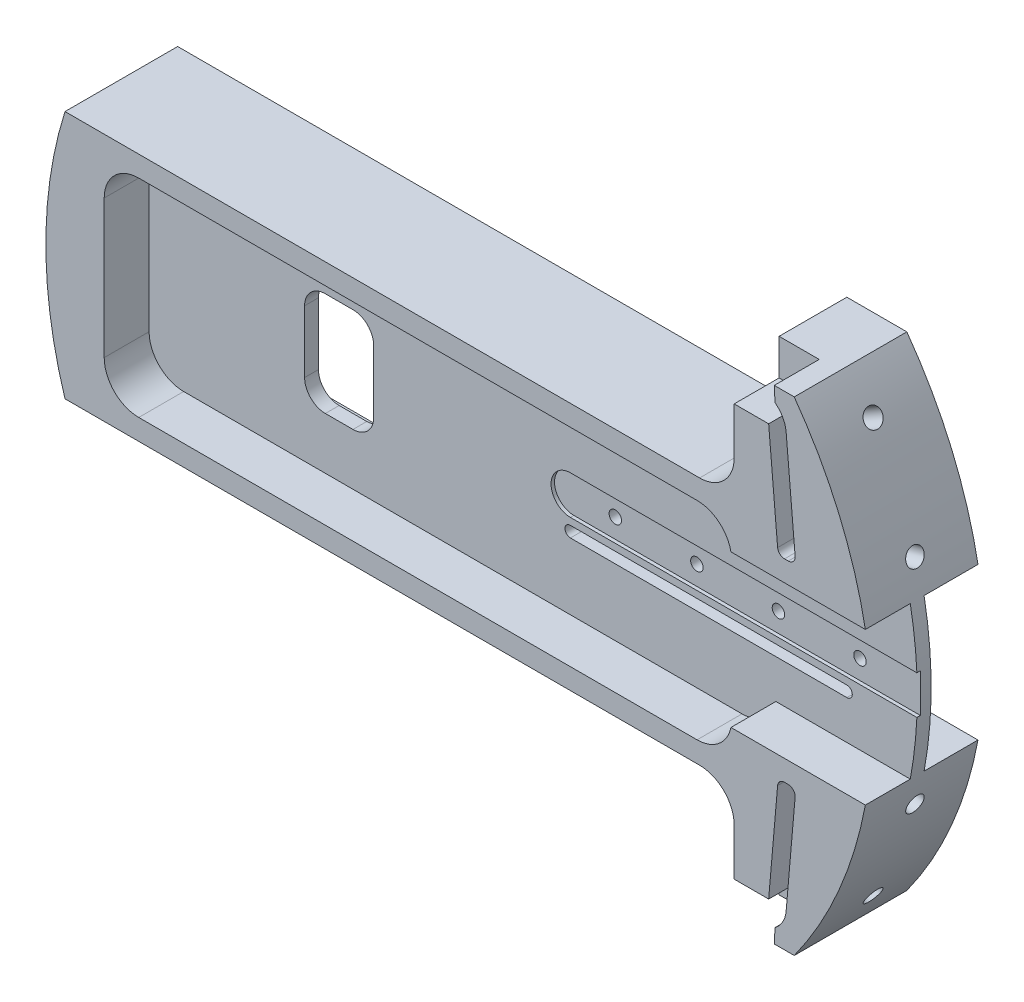
SolidWorks part; units mm, degrees
ref_plane "Front Plane" through (0, 0, 0) normal (0, 0, 1) x (1, 0, 0)
ref_plane "Top Plane" through (0, 0, 0) normal (0, 1, 0) x (1, 0, 0)
ref_plane "Right Plane" through (0, 0, 0) normal (1, 0, 0) x (0, 0, -1)
sketch "Sketch1" plane through (0, 0, 0) normal (0, 0, 1) x (1, 0, 0)
  line L0 (0, 0) -> (91.8237, 0) construction
  line L2 (-71.5726, 25.4) -> (-65.2226, 25.4)
  line L3 (50.546, 44.45) -> (50.546, 22.86)
  line L4 (50.546, -44.45) -> (50.546, -22.86)
  line L5 (44.196, -16.51) -> (-58.8726, -16.51)
  line L6 (50.546, 44.45) -> (61.5792, 44.45)
  line L7 (50.546, -44.45) -> (61.5792, -44.45)
  line L8 (-65.2226, -22.86) -> (-65.2226, -25.4)
  line L9 (44.196, 16.51) -> (-58.8726, 16.51)
  line L10 (-65.2226, 22.86) -> (-65.2226, 25.4)
  line L11 (-71.5726, -25.4) -> (-65.2226, -25.4)
  arc A0 (61.5792, -44.45) -> (61.5792, 44.45) centre (0, 0) ccw
  circle A1 centre (0, 0) radius 75.946 construction
  arc A2 (-71.5726, 25.4) -> (-71.5726, -25.4) centre (0, 0) ccw
  arc A5 (50.546, 22.86) -> (44.196, 16.51) centre (44.196, 22.86) cw
  arc A6 (-58.8726, 16.51) -> (-65.2226, 22.86) centre (-58.8726, 22.86) cw
  arc A7 (50.546, -22.86) -> (44.196, -16.51) centre (44.196, -22.86) ccw
  arc A8 (-58.8726, -16.51) -> (-65.2226, -22.86) centre (-58.8726, -22.86) ccw
  point P6 (75.946, 0)
  point P17 (0, 0)
  point P30 (50.546, -16.51)
  point P33 (-65.2226, -16.51)
  dimension "D1" = 75.946
  dimension "D8" = 151.892
  dimension "D11" = 75.946
  dimension "D13" = 6.35
  dimension "D2" = 27.94
  dimension "D3" = 6.35
  dimension "D4" = 11.0332
  dimension "D5" = 50.8
  dimension "D6" = 88.9
extrude "Boss-Extrude1" add sketch "Sketch1" along normal blind 2.54
sketch "Sketch2" plane through (0, 0, 2.54) normal (0, 0, 1) x (1, 0, 0)
  line L0 (60.2463, 17.78) -> (56.2059, 64.1603) construction
  line L1 (-13.9228, 0) -> (116.9939, 0) construction
  line L2 (35.7924, 17.78) -> (109.7023, 17.78) construction
  line L3 (61.8653, 17.78) -> (60.0951, 38.1)
  line L4 (58.6516, 17.5) -> (56.8815, 37.82)
  line L5 (56.8815, 37.82) -> (50.546, 37.82)
  line L6 (58.0471, 41.7789) -> (57.9008, 44.704)
  line L7 (57.9008, 44.704) -> (61.395, 44.704)
  line L8 (50.546, 37.82) -> (50.546, 16.5667)
  line L9 (50.546, 16.5667) -> (57.3661, 16.5667)
  line L10 (60.7595, 15.0941) -> (60.7595, 13.5449)
  line L11 (60.7595, 13.5449) -> (74.7284, 13.5449)
  line L12 (60.2463, -17.78) -> (56.2059, -64.1603) construction
  line L13 (60.7595, -13.5449) -> (74.7284, -13.5449)
  line L14 (60.7595, -15.0941) -> (60.7595, -13.5449)
  line L15 (50.546, -16.5667) -> (57.3661, -16.5667)
  line L16 (50.546, -37.82) -> (50.546, -16.5667)
  line L17 (57.9008, -44.704) -> (61.395, -44.704)
  line L18 (58.0471, -41.7789) -> (57.9008, -44.704)
  line L19 (56.8815, -37.82) -> (50.546, -37.82)
  line L20 (58.6516, -17.5) -> (56.8815, -37.82)
  line L21 (61.8653, -17.78) -> (60.0951, -38.1)
  line L22 (96.3863, 0) -> (96.3863, 82.276) construction
  arc A0 (61.5792, -44.45) -> (61.5792, 44.45) centre (0, 0) ccw construction
  arc A1 (60.0951, 38.1) -> (58.0471, 41.7789) centre (54.9639, 37.653) ccw
  arc A2 (57.3661, 16.5667) -> (58.6516, 17.5) centre (57.3661, 17.9187) ccw
  arc A3 (61.8653, 17.78) -> (60.7595, 15.0941) centre (58.7167, 17.5057) cw
  arc A4 (74.7284, 13.5449) -> (61.395, 44.704) centre (0, 0) ccw
  arc A5 (74.7284, -13.5449) -> (61.395, -44.704) centre (0, 0) cw
  arc A6 (61.8653, -17.78) -> (60.7595, -15.0941) centre (58.7167, -17.5057) ccw
  arc A7 (57.3661, -16.5667) -> (58.6516, -17.5) centre (57.3661, -17.9187) cw
  arc A8 (60.0951, -38.1) -> (58.0471, -41.7789) centre (54.9639, -37.653) cw
  point P0 (75.946, 0)
  point P1 (60.2463, 17.78)
  point P49 (96.3863, 44.704)
  dimension "D6" = 75.946
  dimension "D1" = 17.78
  dimension "D2" = 15.6997
  dimension "D3" = 85.021
  dimension "D4" = 1.6129
  dimension "D5" = 20.32
  dimension "D7" = 44.704
  dimension "D8" = 44.704
  dimension "D9" = 25.4
extrude "Boss-Extrude2" add sketch "Sketch2" along normal blind 8.255
sketch "Sketch3" plane through (0, 0, 2.54) normal (0, 0, 1) x (1, 0, 0)
  line L0 (-6.3906, 0) -> (92.2963, 0) construction
  line L1 (50.546, 44.45) -> (50.546, 22.86) construction
  line L2 (12.192, -3.55) -> (76.962, -3.55)
  line L3 (12.192, -3.55) -> (12.192, 3.55)
  line L4 (12.192, 3.55) -> (76.962, 3.55)
  line L5 (76.962, -3.55) -> (76.962, 3.55)
  line L6 (12.192, -3.55) -> (76.962, 3.55) construction
  line L7 (12.192, 3.55) -> (76.962, -3.55) construction
  point P3 (44.577, 0)
  dimension "D1" = 7.1
  dimension "D2" = 64.77
  dimension "D3" = 38.354
extrude "Cut-Extrude1" cut sketch "Sketch3" against normal blind 0.635
sketch "Sketch6" plane through (0, 0, 0) normal (0, 0, -1) x (-1, 0, 0)
  line L1 (102.4877, 0) -> (-122.8054, 0) construction
sketch "Sketch7" plane through (0, 0, 0) normal (0, 0, 1) x (1, 0, 0)
  line L0 (0, 0) -> (107.1474, 0) construction
  line L1 (0, 0) -> (65.9911, 38.1) construction
  dimension "D1" = 30
ref_plane "Plane2" through (65.7712, 37.973, 0) normal (0.866, 0.5, 0) x (0, 0, -1)
sketch "Sketch4" plane through (0, 0, 1.905) normal (0, 0, 1) x (1, 0, 0)
  line L0 (12.192, 3.55) -> (12.192, -3.55) construction
  line L1 (-1.4827, 0) -> (103.4049, 0) construction
  circle A0 centre (19.812, 0) radius 1.143
  circle A1 centre (34.798, 0) radius 1.143
  circle A2 centre (49.784, 0) radius 1.143
  circle A3 centre (64.77, 0) radius 1.143
  point P2 (12.192, 0)
  dimension "D2" = 2.286
  dimension "D4" = 14.986
  dimension "D1" = 7.62
  dimension "D5" = 19.812
  dimension "D3" = 4
extrude "Cut-Extrude2" cut sketch "Sketch4" against normal blind 11.43
sketch "Sketch19" plane through (0, 0, 2.54) normal (0, 0, 1) x (1, 0, 0)
  line L0 (-71.5726, -25.4) -> (-65.2226, -25.4) construction
  line L3 (-71.5726, -25.4) -> (-65.2226, -25.4)
  line L4 (-65.2226, -25.4) -> (-65.2226, 25.4)
  line L5 (-65.2226, 25.4) -> (-71.5726, 25.4) construction
  line L6 (-65.2226, 25.4) -> (-71.5726, 25.4)
  circle A0 centre (0, 0) radius 75.946 construction
  arc A3 (-71.5726, 25.4) -> (-71.5726, -25.4) centre (0, 0) ccw
  point P0 (-65.2226, -25.4)
  point P6 (-71.5726, -25.4)
  dimension "D2" = 151.892
  dimension "D1" = 6.35
extrude "Boss-Extrude5" add sketch "Sketch19" along normal blind 8.255
ref_plane "Plane3" through (0, 0, 10.795) normal (0, 0, 1) x (1, 0, 0)
sketch "Sketch22" plane through (0, 0, 10.795) normal (0, 0, 1) x (1, 0, 0)
  line L1 (-75.946, -44.45) -> (75.946, -44.45) construction
  line L2 (-75.946, -44.45) -> (-75.946, 44.45) construction
  line L3 (-75.946, 44.45) -> (75.946, 44.45) construction
  line L4 (75.946, -44.45) -> (75.946, 44.45) construction
  line L5 (-75.946, -44.45) -> (75.946, 44.45) construction
  line L6 (-75.946, 44.45) -> (75.946, -44.45) construction
  point P0 (0, 0)
  dimension "D1" = 88.9
  dimension "D2" = 151.892
sketch "Sketch25" plane through (0, 0, 0) normal (0, 0, 1) x (1, 0, 0)
  line L0 (0, 0) -> (145.0129, 0) construction
  line L1 (0, 0) -> (140.0717, -37.5321) construction
  line L2 (0, 0) -> (125.5848, -72.5064) construction
  circle A0 centre (0, 0) radius 76.2 construction
  point P9 (0, 0)
  dimension "D1" = 152.4
  dimension "D2" = 3
ref_plane "Plane4" through (0, 0, 6.096) normal (0, 0, 1) x (1, 0, 0)
sketch "Sketch27" plane through (0, 0, 6.096) normal (0, 0, 1) x (1, 0, 0)
  line L0 (-98.5098, 0) -> (76.2, 0) construction
  line L1 (0, 0) -> (143.2275, -38.3777) construction
  line L2 (0, 0) -> (128.4143, -74.14) construction
  line L3 (0, 0) -> (143.2275, 38.3777) construction
  line L4 (0, 0) -> (128.4143, 74.14) construction
  line L5 (-95.1532, 25.4962) -> (73.6035, -19.722) construction
  line L6 (-95.1532, -25.4962) -> (73.6035, 19.722) construction
  circle A0 centre (0, 0) radius 76.2 construction
  point P5 (3.2671, -47.4697)
  point P10 (0, 0)
  point P13 (0, 0)
  point P17 (0, 0)
  point P19 (0, 0)
  dimension "D1" = 3
  dimension "D2" = 3
  dimension "D3" = 2
  dimension "D4" = 2
ref_plane "Plane5" through (65.7712, 37.973, 0) normal (0.866, 0.5, 0) x (0, 0, -1)
ref_plane "Plane6" through (73.3582, 19.6563, 0) normal (0.9659, 0.2588, 0) x (0, 0, -1)
ref_plane "Plane7" through (73.3582, -19.6563, 0) normal (0.9659, -0.2588, 0) x (0, 0, -1)
ref_plane "Plane8" through (65.7712, -37.973, 0) normal (0.866, -0.5, 0) x (0, 0, -1)
ref_plane "Plane9" through (0, 0, 0) normal (0, 1, 0) x (1, 0, 0)
ref_plane "Plane10" through (-73.3582, 19.6563, 0) normal (-0.9659, 0.2588, 0) x (0, 0, 1)
ref_plane "Plane11" through (-75.946, 0, 0) normal (-1, 0, 0) x (0, 0, 1)
ref_plane "Plane12" through (-73.3582, -19.6563, 0) normal (-0.9659, -0.2588, 0) x (0, 0, 1)
sketch "Sketch33" plane through (0, 0, 2.54) normal (0, 0, 1) x (1, 0, 0)
  line L0 (44.196, 16.51) -> (-58.8726, 16.51) construction
  line L1 (12.1373, 16.51) -> (-58.8726, 16.51)
  line L2 (44.196, 15.24) -> (-58.8726, 15.24) construction
  line L3 (12.1373, 13.97) -> (-58.8726, 13.97)
  line L4 (0, 0) -> (-34.589, 0) construction
  line L5 (-65.2226, 22.86) -> (-65.2226, 7.62)
  line L6 (12.1373, 13.97) -> (12.1373, 16.51)
  line L7 (12.1373, -13.97) -> (12.1373, -16.51)
  line L8 (44.196, 16.51) -> (-58.8726, 16.51) construction
  line L9 (44.196, -15.24) -> (-58.8726, -15.24) construction
  line L10 (12.1373, -16.51) -> (-58.8726, -16.51)
  line L11 (12.1373, -13.97) -> (-58.8726, -13.97)
  line L12 (-65.2226, -22.86) -> (-65.2226, -7.62)
  arc A0 (-65.2226, 22.86) -> (-58.8726, 16.51) centre (-58.8726, 22.86) ccw construction
  arc A1 (-65.2226, 22.86) -> (-58.8726, 16.51) centre (-58.8726, 22.86) ccw
  arc A2 (-65.2226, 7.62) -> (-58.8726, 13.97) centre (-58.8726, 7.62) cw
  arc A3 (-66.4926, 22.86) -> (-58.8726, 15.24) centre (-58.8726, 22.86) ccw construction
  arc A4 (-65.2226, -7.62) -> (-58.8726, -13.97) centre (-58.8726, -7.62) ccw
  arc A5 (-65.2226, -22.86) -> (-58.8726, -16.51) centre (-58.8726, -22.86) cw
  dimension "D2" = 71.0099
  dimension "D3" = 2.54
  dimension "D1" = 1.27
extrude "Boss-Extrude6" add sketch "Sketch33" along normal up to surface (8.255 mm away) up to face at (-69.4909, 0, 10.795)
sketch "Sketch38" plane through (0, 0, 10.795) normal (0, 0, 1) x (1, 0, 0)
  line L0 (12.1373, -13.97) -> (60.7595, -13.97)
  line L1 (60.7595, -13.5449) -> (60.7595, -15.0941) construction
  line L2 (12.1373, -16.51) -> (44.196, -16.51)
  line L3 (61.8653, 17.78) -> (58.2982, 17.78)
  line L4 (58.2982, -17.78) -> (50.546, -22.86)
  line L5 (60.7595, -13.97) -> (60.7595, -15.0941)
  line L6 (12.1373, -16.51) -> (12.1373, -13.97)
  line L7 (63.627, 0) -> (92.2088, 0) construction
  line L8 (12.1373, 16.51) -> (12.1373, 13.97)
  line L9 (60.7595, 13.97) -> (60.7595, 15.0941)
  line L10 (58.2982, 17.78) -> (50.546, 22.86)
  line L11 (12.1373, 16.51) -> (44.196, 16.51)
  line L12 (12.1373, 13.97) -> (60.7595, 13.97)
  line L14 (61.8653, -17.78) -> (58.2982, -17.78)
  arc A0 (50.546, -22.86) -> (44.196, -16.51) centre (44.196, -22.86) ccw construction
  arc A1 (50.546, -22.86) -> (44.196, -16.51) centre (44.196, -22.86) ccw
  arc A2 (61.8653, -17.78) -> (60.7595, -15.0941) centre (58.7167, -17.5057) ccw construction
  arc A3 (61.8653, -17.78) -> (60.7595, -15.0941) centre (58.7167, -17.5057) ccw
  circle A4 centre (64.77, 0) radius 1.143 construction
  arc A5 (61.8653, 17.78) -> (60.7595, 15.0941) centre (58.7167, 17.5057) cw
  arc A6 (50.546, 22.86) -> (44.196, 16.51) centre (44.196, 22.86) cw
extrude "Boss-Extrude7" add sketch "Sketch38" against normal up to surface (8.255 mm away) up to face at (39.9553, -0.238, 2.54)
sketch "Sketch39" plane through (0, 0, 10.795) normal (0, 0, 1) x (1, 0, 0)
  line L1 (60.7595, -13.97) -> (74.7348, -13.97)
  line L2 (60.7595, -13.97) -> (60.7595, 13.97)
  line L3 (60.7595, 13.97) -> (74.7348, 13.97)
  line L4 (74.7348, -13.97) -> (74.7348, 13.97)
extrude "Cut-Extrude19" cut sketch "Sketch39" against normal up to surface (8.255 mm away) up to face at (22.2, -0.7139, 2.54)
fillet "Fillet2" radius 1.27 4 edges at (58.6273, -17.78, 6.6675) (61.8653, -17.78, 6.6675) (58.6273, 17.78, 6.6675) (61.8653, 17.78, 6.6675)
sketch "Sketch45" plane through (0, 0, 10.795) normal (0, 0, 1) x (1, 0, 0)
  line L0 (-67.721, -22.7159) -> (54.0765, -22.7159)
  line L1 (54.0765, -22.7159) -> (54.0765, -20.1759)
  line L2 (54.0765, -20.1759) -> (-67.721, -20.1759)
  line L3 (-65.2226, -7.62) -> (-65.2226, 7.62) construction
  line L4 (-67.721, -20.1759) -> (-67.721, -22.7159)
  line L5 (-65.2226, 0) -> (-20.8376, 0) construction
  line L6 (-67.721, 20.1759) -> (-67.721, 22.7159)
  line L7 (54.0765, 20.1759) -> (-67.721, 20.1759)
  line L8 (54.0765, 22.7159) -> (54.0765, 20.1759)
  line L9 (-67.721, 22.7159) -> (54.0765, 22.7159)
  dimension "D1" = 2.54
extrude "Boss-Extrude8" add sketch "Sketch45" against normal up to surface (10.795 mm away) up to face at (65.913, 0, 0)
sketch "Sketch46" plane through (0, 0, 10.795) normal (0, 0, 1) x (1, 0, 0)
  line L0 (-64.6274, 20.1759) -> (49.9508, 20.1759) construction
  line L1 (-65.2226, 20.1759) -> (49.9508, 20.1759)
  line L2 (-65.2226, 20.1759) -> (-65.2226, -20.1759)
  line L3 (-65.2226, -20.1759) -> (49.9508, -20.1759)
  line L4 (49.9508, 20.1759) -> (49.9508, -20.1759)
  line L5 (-65.2226, -7.62) -> (-65.2226, 7.62) construction
extrude "Cut-Extrude20" cut sketch "Sketch46" against normal up to surface (8.255 mm away) up to face at (7.459, -1.042, 2.54)
sketch "Sketch48" plane through (0, 0, 2.54) normal (0, 0, 1) x (1, 0, 0)
  line L0 (12.192, 0) -> (-88.754, 0) construction
  line L1 (-65.2226, 20.1759) -> (49.9508, 20.1759)
  line L2 (-65.2226, 20.1759) -> (-65.2226, 13.97)
  line L3 (-65.2226, 13.97) -> (49.9508, 13.97)
  line L4 (49.9508, 20.1759) -> (49.9508, 13.97)
  line L5 (12.192, 3.55) -> (12.192, -3.55) construction
  line L6 (49.9508, -20.1759) -> (49.9508, -13.97)
  line L7 (-65.2226, -13.97) -> (49.9508, -13.97)
  line L8 (-65.2226, -20.1759) -> (-65.2226, -13.97)
  line L9 (-65.2226, -20.1759) -> (49.9508, -20.1759)
extrude "Boss-Extrude9" add sketch "Sketch48" against normal up to surface (2.54 mm away) up to face at (-7.3383, 17.9236, 0)
sketch "Sketch51" plane through (0, 0, 10.795) normal (0, 0, 1) x (1, 0, 0)
  line L0 (-80.7764, 25.4) -> (-80.7764, 22.7159)
  line L1 (-65.2226, 22.7159) -> (-80.7764, 22.7159)
  line L2 (63.627, 0) -> (102.0102, 0) construction
  line L3 (50.546, -22.7159) -> (-65.2226, -22.7159)
  line L4 (50.546, -22.7159) -> (50.546, -25.4)
  line L5 (50.546, -25.4) -> (-65.2226, -25.4)
  line L6 (-65.2226, 25.4) -> (-80.7764, 25.4)
  line L7 (50.546, 25.4) -> (-65.2226, 25.4)
  line L8 (50.546, 22.7159) -> (50.546, 25.4)
  line L9 (-65.2226, -25.4) -> (-80.7764, -25.4)
  line L10 (50.546, 22.7159) -> (-65.2226, 22.7159)
  line L11 (-65.2226, -22.7159) -> (-80.7764, -22.7159)
  line L12 (-80.7764, -25.4) -> (-80.7764, -22.7159)
  circle A0 centre (64.77, 0) radius 1.143 construction
extrude "Cut-Extrude24" cut sketch "Sketch51" against normal blind 43.688
sketch "Sketch52" plane through (0, 0, 2.54) normal (0, 0, 1) x (1, 0, 0)
  line L0 (12.192, 3.55) -> (12.192, -3.55) construction
  line L1 (12.192, -3.55) -> (12.192, 3.55)
  arc A0 (12.192, 3.55) -> (12.192, -3.55) centre (12.192, 0) ccw
extrude "Cut-Extrude25" cut sketch "Sketch52" against normal up to surface (0.635 mm away) up to face at (65.913, 0, 1.905)
sketch "Sketch53" plane through (0, 0, 0) normal (0, 0, -1) x (-1, 0, 0)
  line L0 (-63.627, 0) -> (-88.114, 0) construction
  line L1 (-50.546, -44.45) -> (-63.8852, -44.45)
  line L2 (-50.546, -44.45) -> (-50.546, -49.2353)
  line L3 (-50.546, -49.2353) -> (-63.8852, -49.2353)
  line L4 (-63.8852, -44.45) -> (-63.8852, -49.2353)
  line L5 (-63.8852, 44.45) -> (-63.8852, 49.2353)
  line L6 (-50.546, 49.2353) -> (-63.8852, 49.2353)
  line L7 (-50.546, 44.45) -> (-50.546, 49.2353)
  line L8 (-50.546, 44.45) -> (-63.8852, 44.45)
  circle A0 centre (-64.77, 0) radius 1.143 construction
extrude "Cut-Extrude26" cut sketch "Sketch53" against normal blind 43.688
sketch "Sketch58" plane through (0, 0, 10.795) normal (0, 0, 1) x (1, 0, 0)
  line L2 (-65.2226, 0) -> (-92.2383, 0) construction
  line L3 (-65.2226, -20.1759) -> (-65.2226, 20.1759) construction
  line L4 (50.546, 37.82) -> (50.546, 22.7159) construction
  line L5 (50.546, 22.86) -> (-72.4239, 22.86)
  line L6 (50.546, 22.86) -> (50.546, 19.05)
  line L7 (50.546, 19.05) -> (-65.2226, 19.05)
  line L8 (-72.4692, 22.7159) -> (-65.2226, 22.7159)
  line L9 (-65.2226, -22.7159) -> (-65.2226, -19.05)
  line L10 (50.546, 22.7159) -> (-72.4692, 22.7159) construction
  line L11 (-65.2226, 22.7159) -> (-65.2226, 19.05)
  line L12 (-72.4692, -22.7159) -> (-65.2226, -22.7159)
  line L13 (50.546, -19.05) -> (-65.2226, -19.05)
  line L14 (50.546, -22.86) -> (50.546, -19.05)
  line L15 (50.546, -22.86) -> (-72.4239, -22.86)
  arc A0 (-72.4239, 22.86) -> (-72.4692, 22.7159) centre (0, 0) ccw
  arc A2 (-72.4239, -22.86) -> (-72.4692, -22.7159) centre (0, 0) cw
  dimension "D1" = 3.81
  dimension "D2" = 22.86
extrude "Boss-Extrude10" add sketch "Sketch58" against normal up to surface (10.795 mm away) up to face at (23.9117, 0, 0)
fillet "Fillet8" radius 6.35 6 edges at (50.546, 22.86, 5.3975) (50.546, -22.86, 5.3975) (49.9508, 19.05, 6.6675) (49.9508, -19.05, 6.6675) (-65.2226, 19.05, 6.6675) (-65.2226, -19.05, 6.6675)
sketch "Sketch59" plane through (0, 0, 10.795) normal (0, 0, 1) x (1, 0, 0)
  line L1 (50.546, -29.21) -> (50.546, -44.45)
  line L2 (50.546, -44.45) -> (61.5792, -44.45)
  line L3 (50.546, 29.21) -> (50.546, 44.45)
  line L4 (50.546, 44.45) -> (61.5792, 44.45)
  line L21 (74.6501, -13.97) -> (49.9508, -13.97)
  line L22 (43.7291, -19.05) -> (-58.8726, -19.05)
  line L23 (-65.2226, -12.7) -> (-65.2226, 12.7)
  line L24 (-58.8726, 19.05) -> (43.7291, 19.05)
  line L25 (49.9508, 13.97) -> (74.6501, 13.97)
  line L26 (61.5792, 44.45) -> (57.9135, 44.45)
  line L27 (57.9135, 44.45) -> (58.0471, 41.7789)
  line L28 (60.0951, 38.1) -> (61.745, 19.1602)
  line L29 (60.4798, 17.78) -> (59.7914, 17.78)
  line L30 (58.5262, 18.9398) -> (56.8815, 37.82)
  line L31 (56.8815, 37.82) -> (50.546, 37.82)
  line L32 (50.546, 37.82) -> (50.546, 29.21)
  line L33 (44.196, 22.86) -> (-72.4239, 22.86)
  line L34 (-72.4239, -22.86) -> (44.196, -22.86)
  line L35 (50.546, -29.21) -> (50.546, -37.82)
  line L36 (50.546, -37.82) -> (56.8815, -37.82)
  line L37 (56.8815, -37.82) -> (58.5262, -18.9398)
  line L38 (59.7914, -17.78) -> (60.4798, -17.78)
  line L39 (61.745, -19.1602) -> (60.0951, -38.1)
  line L40 (58.0471, -41.7789) -> (57.9135, -44.45)
  line L41 (57.9135, -44.45) -> (61.5792, -44.45)
  line L42 (74.6501, -13.97) -> (49.9508, -13.97)
  line L43 (43.7291, -19.05) -> (-58.8726, -19.05)
  line L44 (-65.2226, -12.7) -> (-65.2226, 12.7)
  line L45 (-58.8726, 19.05) -> (43.7291, 19.05)
  line L46 (49.9508, 13.97) -> (74.6501, 13.97)
  line L54 (44.196, 22.86) -> (-72.4239, 22.86)
  line L55 (-72.4239, -22.86) -> (44.196, -22.86)
  arc A15 (43.7291, -19.05) -> (49.9508, -13.97) centre (43.7291, -12.7) ccw
  arc A16 (-65.2226, -12.7) -> (-58.8726, -19.05) centre (-58.8726, -12.7) ccw
  arc A17 (-58.8726, 19.05) -> (-65.2226, 12.7) centre (-58.8726, 12.7) ccw
  arc A18 (49.9508, 13.97) -> (43.7291, 19.05) centre (43.7291, 12.7) ccw
  arc A19 (74.6501, 13.97) -> (61.5792, 44.45) centre (0, 0) ccw
  arc A20 (60.0951, 38.1) -> (58.0471, 41.7789) centre (54.9639, 37.653) ccw
  arc A21 (60.4798, 17.78) -> (61.745, 19.1602) centre (60.4798, 19.05) ccw
  arc A22 (58.5262, 18.9398) -> (59.7914, 17.78) centre (59.7914, 19.05) ccw
  arc A23 (44.196, 22.86) -> (50.546, 29.21) centre (44.196, 29.21) ccw
  arc A24 (-72.4239, 22.86) -> (-72.4239, -22.86) centre (0, 0) ccw
  arc A25 (50.546, -29.21) -> (44.196, -22.86) centre (44.196, -29.21) ccw
  arc A26 (59.7914, -17.78) -> (58.5262, -18.9398) centre (59.7914, -19.05) ccw
  arc A27 (61.745, -19.1602) -> (60.4798, -17.78) centre (60.4798, -19.05) ccw
  arc A28 (58.0471, -41.7789) -> (60.0951, -38.1) centre (54.9639, -37.653) ccw
  arc A29 (61.5792, -44.45) -> (74.6501, -13.97) centre (0, 0) ccw
  arc A30 (43.7291, -19.05) -> (49.9508, -13.97) centre (43.7291, -12.7) ccw
  arc A31 (-65.2226, -12.7) -> (-58.8726, -19.05) centre (-58.8726, -12.7) ccw
  arc A32 (-58.8726, 19.05) -> (-65.2226, 12.7) centre (-58.8726, 12.7) ccw
  arc A33 (49.9508, 13.97) -> (43.7291, 19.05) centre (43.7291, 12.7) ccw
  arc A34 (74.6501, 13.97) -> (61.5792, 44.45) centre (0, 0) ccw
  arc A38 (44.196, 22.86) -> (50.546, 29.21) centre (44.196, 29.21) ccw
  arc A39 (-72.4239, 22.86) -> (-72.4239, -22.86) centre (0, 0) ccw
  arc A40 (50.546, -29.21) -> (44.196, -22.86) centre (44.196, -29.21) ccw
  arc A44 (61.5792, -44.45) -> (74.6501, -13.97) centre (0, 0) ccw
  dimension "D1" = 0
extrude "Boss-Extrude13" add sketch "Sketch59" against normal blind 9.906 from surface starting at face at (28.2362, 0, 0)
sketch "Sketch60" plane through (0, 0, 10.795) normal (0, 0, 1) x (1, 0, 0)
sketch "Sketch61" plane through (0, 0, 2.54) normal (0, 0, 1) x (1, 0, 0)
  line L0 (12.192, -3.55) -> (75.863, -3.55) construction
  line L1 (12.192, -4.82) -> (62.992, -4.82)
  line L3 (12.192, -6.82) -> (62.992, -6.82)
  arc A0 (12.192, -4.82) -> (12.192, -6.82) centre (12.192, -5.82) ccw
  arc A1 (62.992, -4.82) -> (62.992, -6.82) centre (62.992, -5.82) cw
  dimension "D3" = 50.8
  dimension "D1" = 2
  dimension "D2" = 1.27
extrude "Cut-Extrude27" cut sketch "Sketch61" against normal blind 12.192
sketch "Sketch62" plane through (0, 0, 2.54) normal (0, 0, 1) x (1, 0, 0)
  line L0 (-65.2226, -12.7) -> (-65.2226, 12.7) construction
  line L1 (-23.9476, -9.525) -> (-36.6476, -9.525)
  line L2 (-23.9476, -9.525) -> (-23.9476, 9.525)
  line L3 (-23.9476, 9.525) -> (-36.6476, 9.525)
  line L4 (-36.6476, -9.525) -> (-36.6476, 9.525)
  point P4 (-30.2976, 9.525)
  point P5 (-36.6476, 0)
  point P8 (-65.2226, 0)
  dimension "D2" = 28.575
  dimension "D1" = 19.05
  dimension "D3" = 12.7
extrude "Cut-Extrude28" cut sketch "Sketch62" against normal blind 12.192
fillet "Fillet9" radius 3.81 4 edges at (-36.6476, 9.525, 1.27) (-23.9476, 9.525, 1.27) (-23.9476, -9.525, 1.27) (-36.6476, -9.525, 1.27)
sketch "Sketch63" plane through (65.7712, 37.973, 0) normal (0.866, 0.5, 0) x (0, 0, -1)
  line L0 (-10.795, 7.7053) -> (9.906, 7.7053) construction
  circle A0 centre (-0.4445, 0.0853) radius 1.651
  point P7 (-0.4445, 7.7053)
  dimension "D1" = 3.302
  dimension "D3" = 7.62
extrude "Cut-Extrude30" cut sketch "Sketch63" against normal blind 7.62
sketch "Sketch64" plane through (73.3582, 19.6563, 0) normal (0.9659, 0.2588, 0) x (0, 0, -1)
  line L0 (-10.795, -5.8269) -> (-2.54, -5.8269) construction
  line L1 (-10.795, 26.9975) -> (-10.795, -5.8269) construction
  circle A0 centre (-0.381, 0.0151) radius 1.651
  dimension "D1" = 3.302
  dimension "D2" = 5.842
  dimension "D3" = 10.414
extrude "Cut-Extrude31" cut sketch "Sketch64" against normal blind 10.16
mirror "Mirror1" about plane through (0, 0, 0) normal (0, 1, 0) of "Cut-Extrude30", "Cut-Extrude31"
sketch "Sketch65" plane through (-75.946, 0, 0) normal (-1, 0, 0) x (0, 0, 1)
  line L0 (-9.906, 22.86) -> (-9.906, -22.86) construction
  circle A0 centre (0.508, 0) radius 1.651
  dimension "D1" = 3.302
  dimension "D2" = 10.414
extrude "Cut-Extrude32" cut sketch "Sketch65" against normal blind 10.16
sketch "Sketch66" plane through (-73.3582, -19.6563, 0) normal (-0.9659, -0.2588, 0) x (0, 0, 1)
  line L0 (-9.906, -3.3364) -> (10.795, -3.3364) construction
  line L1 (-9.906, 40.8257) -> (-9.906, -3.3364) construction
  circle A0 centre (0.508, -0.0344) radius 1.651
  dimension "D1" = 3.302
  dimension "D2" = 3.302
  dimension "D3" = 10.414
extrude "Cut-Extrude33" cut sketch "Sketch66" against normal blind 8.89
sketch "Sketch67" plane through (-73.3582, 19.6563, 0) normal (-0.9659, 0.2588, 0) x (0, 0, 1)
  line L0 (-9.906, 3.3364) -> (10.795, 3.3364) construction
  line L1 (-9.906, 3.3364) -> (-9.906, -40.8257) construction
  circle A0 centre (0.508, 0) radius 1.651
  dimension "D1" = 3.302
  dimension "D2" = 3.3364
  dimension "D3" = 10.414
extrude "Cut-Extrude34" cut sketch "Sketch67" against normal blind 8.89
equation "\"0.15inin\"=0.2"
equation "\"0.45inin\"=0.35"
equation "\"0.55inin\"=0.45"
equation "\"0.125inin\"=0.325"
